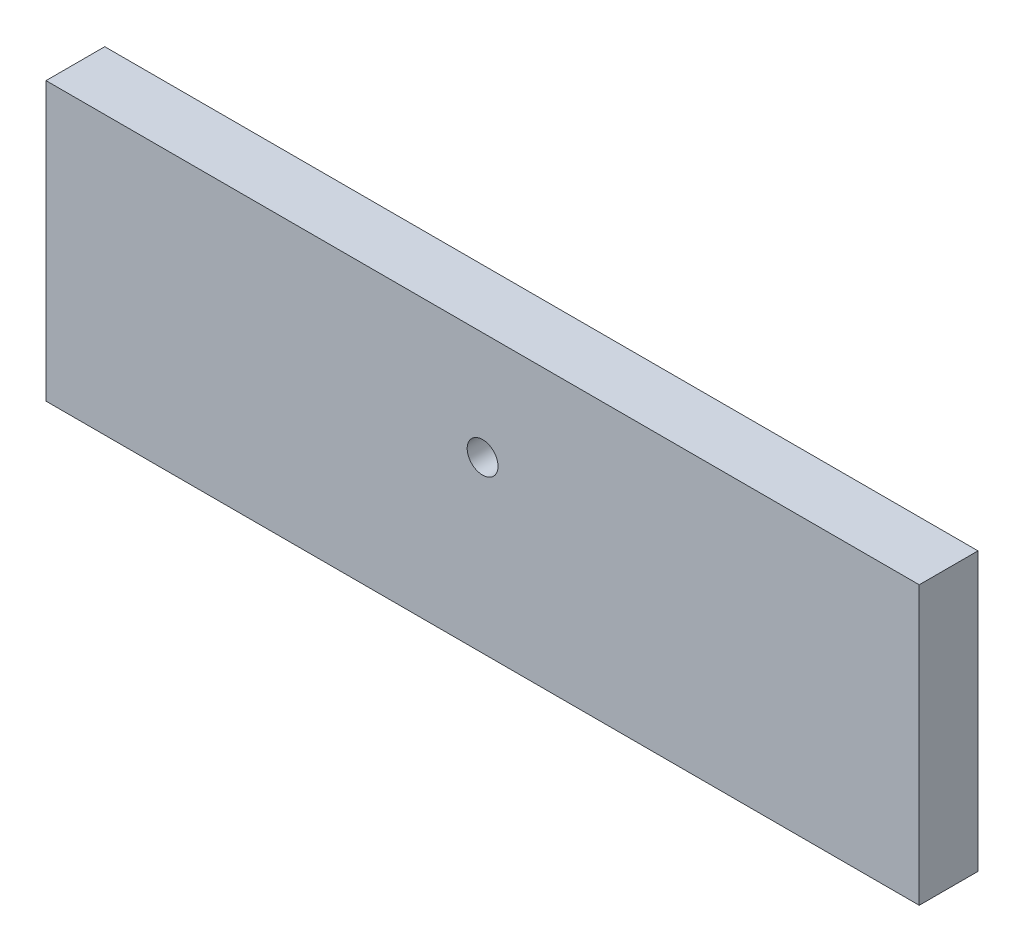
SolidWorks part; units mm, degrees
ref_plane "Front Plane" through (0, 0, 0) normal (0, 0, 1) x (1, 0, 0)
ref_plane "Top Plane" through (0, 0, 0) normal (0, 1, 0) x (1, 0, 0)
ref_plane "Right Plane" through (0, 0, 0) normal (1, 0, 0) x (0, 0, -1)
sketch "Sketch1" plane through (0, 0, 0) normal (0, 0, 1) x (1, 0, 0)
  line L1 (-141.55, 90) -> (141.55, 90)
  line L2 (-141.55, 90) -> (-141.55, 0)
  line L3 (-141.55, 0) -> (141.55, 0)
  line L4 (141.55, 90) -> (141.55, 0)
  dimension "D1" = 90
  dimension "D2" = 283.1
extrude "Boss-Extrude1" add sketch "Sketch1" along normal blind 19.05
sketch "Sketch2" plane through (0, 0, 19.05) normal (0, 0, 1) x (1, 0, 0)
  circle A0 centre (0, 55) radius 5
extrude "Cut-Extrude1" cut sketch "Sketch2" against normal through all contours A0
